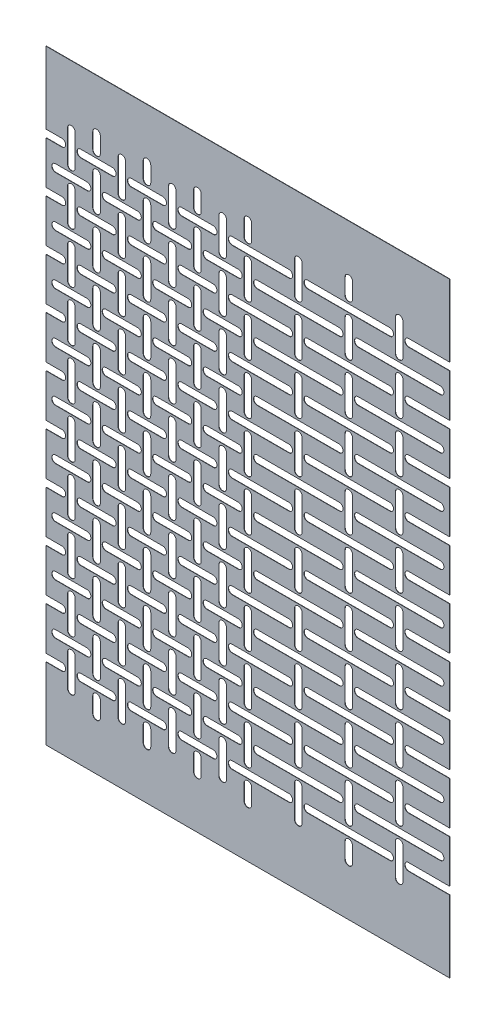
SolidWorks part; units mm, degrees
ref_plane "Front Plane" through (0, 0, 0) normal (0, 0, 1) x (1, 0, 0)
ref_plane "Top Plane" through (0, 0, 0) normal (0, 1, 0) x (1, 0, 0)
ref_plane "Right Plane" through (0, 0, 0) normal (1, 0, 0) x (0, 0, -1)
sketch "Model" plane through (0, 0, 0) normal (0, 0, 1) x (1, 0, 0)
  line L0 (0, 31.5) -> (6.25, 31.5)
  line L1 (0, 28.5) -> (6.25, 28.5)
  line L2 (13.75, 31.5) -> (26.25, 31.5)
  line L3 (13.75, 28.5) -> (26.25, 28.5)
  line L4 (33.75, 31.5) -> (46.25, 31.5)
  line L5 (33.75, 28.5) -> (46.25, 28.5)
  line L6 (53.75, 31.5) -> (66.25, 31.5)
  line L7 (53.75, 28.5) -> (66.25, 28.5)
  line L8 (73.75, 31.5) -> (80, 31.5)
  line L9 (73.75, 28.5) -> (80, 28.5)
  line L10 (3.75, 41.5) -> (16.25, 41.5)
  line L11 (3.75, 38.5) -> (16.25, 38.5)
  line L12 (23.75, 41.5) -> (36.25, 41.5)
  line L13 (23.75, 38.5) -> (36.25, 38.5)
  line L14 (43.75, 41.5) -> (56.25, 41.5)
  line L15 (43.75, 38.5) -> (56.25, 38.5)
  line L16 (63.75, 41.5) -> (76.25, 41.5)
  line L17 (63.75, 38.5) -> (76.25, 38.5)
  line L18 (0, 51.5) -> (6.25, 51.5)
  line L19 (0, 48.5) -> (6.25, 48.5)
  line L20 (13.75, 51.5) -> (26.25, 51.5)
  line L21 (13.75, 48.5) -> (26.25, 48.5)
  line L22 (33.75, 51.5) -> (46.25, 51.5)
  line L23 (33.75, 48.5) -> (46.25, 48.5)
  line L24 (53.75, 51.5) -> (66.25, 51.5)
  line L25 (53.75, 48.5) -> (66.25, 48.5)
  line L26 (73.75, 51.5) -> (80, 51.5)
  line L27 (73.75, 48.5) -> (80, 48.5)
  line L28 (3.75, 61.5) -> (16.25, 61.5)
  line L29 (3.75, 58.5) -> (16.25, 58.5)
  line L30 (23.75, 61.5) -> (36.25, 61.5)
  line L31 (23.75, 58.5) -> (36.25, 58.5)
  line L32 (43.75, 61.5) -> (56.25, 61.5)
  line L33 (43.75, 58.5) -> (56.25, 58.5)
  line L34 (63.75, 61.5) -> (76.25, 61.5)
  line L35 (63.75, 58.5) -> (76.25, 58.5)
  line L36 (0, 71.5) -> (6.25, 71.5)
  line L37 (0, 68.5) -> (6.25, 68.5)
  line L38 (13.75, 71.5) -> (26.25, 71.5)
  line L39 (13.75, 68.5) -> (26.25, 68.5)
  line L40 (33.75, 71.5) -> (46.25, 71.5)
  line L41 (33.75, 68.5) -> (46.25, 68.5)
  line L42 (53.75, 71.5) -> (66.25, 71.5)
  line L43 (53.75, 68.5) -> (66.25, 68.5)
  line L44 (73.75, 71.5) -> (80, 71.5)
  line L45 (73.75, 68.5) -> (80, 68.5)
  line L46 (3.75, 81.5) -> (16.25, 81.5)
  line L47 (3.75, 78.5) -> (16.25, 78.5)
  line L48 (23.75, 81.5) -> (36.25, 81.5)
  line L49 (23.75, 78.5) -> (36.25, 78.5)
  line L50 (43.75, 81.5) -> (56.25, 81.5)
  line L51 (43.75, 78.5) -> (56.25, 78.5)
  line L52 (63.75, 81.5) -> (76.25, 81.5)
  line L53 (63.75, 78.5) -> (76.25, 78.5)
  line L54 (0, 91.5) -> (6.25, 91.5)
  line L55 (0, 88.5) -> (6.25, 88.5)
  line L56 (13.75, 91.5) -> (26.25, 91.5)
  line L57 (13.75, 88.5) -> (26.25, 88.5)
  line L58 (33.75, 91.5) -> (46.25, 91.5)
  line L59 (33.75, 88.5) -> (46.25, 88.5)
  line L60 (53.75, 91.5) -> (66.25, 91.5)
  line L61 (53.75, 88.5) -> (66.25, 88.5)
  line L62 (73.75, 91.5) -> (80, 91.5)
  line L63 (73.75, 88.5) -> (80, 88.5)
  line L64 (3.75, 101.5) -> (16.25, 101.5)
  line L65 (3.75, 98.5) -> (16.25, 98.5)
  line L66 (23.75, 101.5) -> (36.25, 101.5)
  line L67 (23.75, 98.5) -> (36.25, 98.5)
  line L68 (43.75, 101.5) -> (56.25, 101.5)
  line L69 (43.75, 98.5) -> (56.25, 98.5)
  line L70 (63.75, 101.5) -> (76.25, 101.5)
  line L71 (63.75, 98.5) -> (76.25, 98.5)
  line L72 (0, 111.5) -> (6.25, 111.5)
  line L73 (0, 108.5) -> (6.25, 108.5)
  line L74 (13.75, 111.5) -> (26.25, 111.5)
  line L75 (13.75, 108.5) -> (26.25, 108.5)
  line L76 (33.75, 111.5) -> (46.25, 111.5)
  line L77 (33.75, 108.5) -> (46.25, 108.5)
  line L78 (53.75, 111.5) -> (66.25, 111.5)
  line L79 (53.75, 108.5) -> (66.25, 108.5)
  line L80 (73.75, 111.5) -> (80, 111.5)
  line L81 (73.75, 108.5) -> (80, 108.5)
  line L82 (3.75, 121.5) -> (16.25, 121.5)
  line L83 (3.75, 118.5) -> (16.25, 118.5)
  line L84 (23.75, 121.5) -> (36.25, 121.5)
  line L85 (23.75, 118.5) -> (36.25, 118.5)
  line L86 (43.75, 121.5) -> (56.25, 121.5)
  line L87 (43.75, 118.5) -> (56.25, 118.5)
  line L88 (63.75, 121.5) -> (76.25, 121.5)
  line L89 (63.75, 118.5) -> (76.25, 118.5)
  line L90 (0, 131.5) -> (6.25, 131.5)
  line L91 (0, 128.5) -> (6.25, 128.5)
  line L92 (13.75, 131.5) -> (26.25, 131.5)
  line L93 (13.75, 128.5) -> (26.25, 128.5)
  line L94 (33.75, 131.5) -> (46.25, 131.5)
  line L95 (33.75, 128.5) -> (46.25, 128.5)
  line L96 (53.75, 131.5) -> (66.25, 131.5)
  line L97 (53.75, 128.5) -> (66.25, 128.5)
  line L98 (73.75, 131.5) -> (80, 131.5)
  line L99 (73.75, 128.5) -> (80, 128.5)
  line L100 (3.75, 141.5) -> (16.25, 141.5)
  line L101 (3.75, 138.5) -> (16.25, 138.5)
  line L102 (23.75, 141.5) -> (36.25, 141.5)
  line L103 (23.75, 138.5) -> (36.25, 138.5)
  line L104 (43.75, 141.5) -> (56.25, 141.5)
  line L105 (43.75, 138.5) -> (56.25, 138.5)
  line L106 (63.75, 141.5) -> (76.25, 141.5)
  line L107 (63.75, 138.5) -> (76.25, 138.5)
  line L108 (0, 151.5) -> (6.25, 151.5)
  line L109 (0, 148.5) -> (6.25, 148.5)
  line L110 (13.75, 151.5) -> (26.25, 151.5)
  line L111 (13.75, 148.5) -> (26.25, 148.5)
  line L112 (33.75, 151.5) -> (46.25, 151.5)
  line L113 (33.75, 148.5) -> (46.25, 148.5)
  line L114 (53.75, 151.5) -> (66.25, 151.5)
  line L115 (53.75, 148.5) -> (66.25, 148.5)
  line L116 (73.75, 151.5) -> (80, 151.5)
  line L117 (73.75, 148.5) -> (80, 148.5)
  line L118 (3.75, 161.5) -> (16.25, 161.5)
  line L119 (3.75, 158.5) -> (16.25, 158.5)
  line L120 (23.75, 161.5) -> (36.25, 161.5)
  line L121 (23.75, 158.5) -> (36.25, 158.5)
  line L122 (43.75, 161.5) -> (56.25, 161.5)
  line L123 (43.75, 158.5) -> (56.25, 158.5)
  line L124 (63.75, 161.5) -> (76.25, 161.5)
  line L125 (63.75, 158.5) -> (76.25, 158.5)
  line L126 (0, 171.5) -> (6.25, 171.5)
  line L127 (0, 168.5) -> (6.25, 168.5)
  line L128 (13.75, 171.5) -> (26.25, 171.5)
  line L129 (13.75, 168.5) -> (26.25, 168.5)
  line L130 (33.75, 171.5) -> (46.25, 171.5)
  line L131 (33.75, 168.5) -> (46.25, 168.5)
  line L132 (53.75, 171.5) -> (66.25, 171.5)
  line L133 (53.75, 168.5) -> (66.25, 168.5)
  line L134 (73.75, 171.5) -> (80, 171.5)
  line L135 (73.75, 168.5) -> (80, 168.5)
  line L136 (3.75, 181.5) -> (16.25, 181.5)
  line L137 (3.75, 178.5) -> (16.25, 178.5)
  line L138 (23.75, 181.5) -> (36.25, 181.5)
  line L139 (23.75, 178.5) -> (36.25, 178.5)
  line L140 (43.75, 181.5) -> (56.25, 181.5)
  line L141 (43.75, 178.5) -> (56.25, 178.5)
  line L142 (63.75, 181.5) -> (76.25, 181.5)
  line L143 (63.75, 178.5) -> (76.25, 178.5)
  line L144 (0, 191.5) -> (6.25, 191.5)
  line L145 (0, 188.5) -> (6.25, 188.5)
  line L146 (13.75, 191.5) -> (26.25, 191.5)
  line L147 (13.75, 188.5) -> (26.25, 188.5)
  line L148 (33.75, 191.5) -> (46.25, 191.5)
  line L149 (33.75, 188.5) -> (46.25, 188.5)
  line L150 (53.75, 191.5) -> (66.25, 191.5)
  line L151 (53.75, 188.5) -> (66.25, 188.5)
  line L152 (73.75, 191.5) -> (80, 191.5)
  line L153 (73.75, 188.5) -> (80, 188.5)
  line L154 (3.75, 201.5) -> (16.25, 201.5)
  line L155 (3.75, 198.5) -> (16.25, 198.5)
  line L156 (23.75, 201.5) -> (36.25, 201.5)
  line L157 (23.75, 198.5) -> (36.25, 198.5)
  line L158 (43.75, 201.5) -> (56.25, 201.5)
  line L159 (43.75, 198.5) -> (56.25, 198.5)
  line L160 (63.75, 201.5) -> (76.25, 201.5)
  line L161 (63.75, 198.5) -> (76.25, 198.5)
  line L162 (0, 211.5) -> (6.25, 211.5)
  line L163 (0, 208.5) -> (6.25, 208.5)
  line L164 (13.75, 211.5) -> (26.25, 211.5)
  line L165 (13.75, 208.5) -> (26.25, 208.5)
  line L166 (33.75, 211.5) -> (46.25, 211.5)
  line L167 (33.75, 208.5) -> (46.25, 208.5)
  line L168 (53.75, 211.5) -> (66.25, 211.5)
  line L169 (53.75, 208.5) -> (66.25, 208.5)
  line L170 (73.75, 211.5) -> (80, 211.5)
  line L171 (73.75, 208.5) -> (80, 208.5)
  line L172 (11.5, 23.75) -> (11.5, 36.25)
  line L173 (8.5, 23.75) -> (8.5, 36.25)
  line L174 (11.5, 43.75) -> (11.5, 56.25)
  line L175 (8.5, 43.75) -> (8.5, 56.25)
  line L176 (11.5, 63.75) -> (11.5, 76.25)
  line L177 (8.5, 63.75) -> (8.5, 76.25)
  line L178 (11.5, 83.75) -> (11.5, 96.25)
  line L179 (8.5, 83.75) -> (8.5, 96.25)
  line L180 (11.5, 103.75) -> (11.5, 116.25)
  line L181 (8.5, 103.75) -> (8.5, 116.25)
  line L182 (11.5, 123.75) -> (11.5, 136.25)
  line L183 (8.5, 123.75) -> (8.5, 136.25)
  line L184 (11.5, 143.75) -> (11.5, 156.25)
  line L185 (8.5, 143.75) -> (8.5, 156.25)
  line L186 (11.5, 163.75) -> (11.5, 176.25)
  line L187 (8.5, 163.75) -> (8.5, 176.25)
  line L188 (11.5, 183.75) -> (11.5, 196.25)
  line L189 (8.5, 183.75) -> (8.5, 196.25)
  line L190 (11.5, 203.75) -> (11.5, 216.25)
  line L191 (8.5, 203.75) -> (8.5, 216.25)
  line L192 (21.5, 20) -> (21.5, 26.25)
  line L193 (18.5, 20) -> (18.5, 26.25)
  line L194 (21.5, 33.75) -> (21.5, 46.25)
  line L195 (18.5, 33.75) -> (18.5, 46.25)
  line L196 (21.5, 53.75) -> (21.5, 66.25)
  line L197 (18.5, 53.75) -> (18.5, 66.25)
  line L198 (21.5, 73.75) -> (21.5, 86.25)
  line L199 (18.5, 73.75) -> (18.5, 86.25)
  line L200 (21.5, 93.75) -> (21.5, 106.25)
  line L201 (18.5, 93.75) -> (18.5, 106.25)
  line L202 (21.5, 113.75) -> (21.5, 126.25)
  line L203 (18.5, 113.75) -> (18.5, 126.25)
  line L204 (21.5, 133.75) -> (21.5, 146.25)
  line L205 (18.5, 133.75) -> (18.5, 146.25)
  line L206 (21.5, 153.75) -> (21.5, 166.25)
  line L207 (18.5, 153.75) -> (18.5, 166.25)
  line L208 (21.5, 173.75) -> (21.5, 186.25)
  line L209 (18.5, 173.75) -> (18.5, 186.25)
  line L210 (21.5, 193.75) -> (21.5, 206.25)
  line L211 (18.5, 193.75) -> (18.5, 206.25)
  line L212 (21.5, 213.75) -> (21.5, 220)
  line L213 (18.5, 213.75) -> (18.5, 220)
  line L214 (31.5, 23.75) -> (31.5, 36.25)
  line L215 (28.5, 23.75) -> (28.5, 36.25)
  line L216 (31.5, 43.75) -> (31.5, 56.25)
  line L217 (28.5, 43.75) -> (28.5, 56.25)
  line L218 (31.5, 63.75) -> (31.5, 76.25)
  line L219 (28.5, 63.75) -> (28.5, 76.25)
  line L220 (31.5, 83.75) -> (31.5, 96.25)
  line L221 (28.5, 83.75) -> (28.5, 96.25)
  line L222 (31.5, 103.75) -> (31.5, 116.25)
  line L223 (28.5, 103.75) -> (28.5, 116.25)
  line L224 (31.5, 123.75) -> (31.5, 136.25)
  line L225 (28.5, 123.75) -> (28.5, 136.25)
  line L226 (31.5, 143.75) -> (31.5, 156.25)
  line L227 (28.5, 143.75) -> (28.5, 156.25)
  line L228 (31.5, 163.75) -> (31.5, 176.25)
  line L229 (28.5, 163.75) -> (28.5, 176.25)
  line L230 (31.5, 183.75) -> (31.5, 196.25)
  line L231 (28.5, 183.75) -> (28.5, 196.25)
  line L232 (31.5, 203.75) -> (31.5, 216.25)
  line L233 (28.5, 203.75) -> (28.5, 216.25)
  line L234 (41.5, 20) -> (41.5, 26.25)
  line L235 (38.5, 20) -> (38.5, 26.25)
  line L236 (41.5, 33.75) -> (41.5, 46.25)
  line L237 (38.5, 33.75) -> (38.5, 46.25)
  line L238 (41.5, 53.75) -> (41.5, 66.25)
  line L239 (38.5, 53.75) -> (38.5, 66.25)
  line L240 (41.5, 73.75) -> (41.5, 86.25)
  line L241 (38.5, 73.75) -> (38.5, 86.25)
  line L242 (41.5, 93.75) -> (41.5, 106.25)
  line L243 (38.5, 93.75) -> (38.5, 106.25)
  line L244 (41.5, 113.75) -> (41.5, 126.25)
  line L245 (38.5, 113.75) -> (38.5, 126.25)
  line L246 (41.5, 133.75) -> (41.5, 146.25)
  line L247 (38.5, 133.75) -> (38.5, 146.25)
  line L248 (41.5, 153.75) -> (41.5, 166.25)
  line L249 (38.5, 153.75) -> (38.5, 166.25)
  line L250 (41.5, 173.75) -> (41.5, 186.25)
  line L251 (38.5, 173.75) -> (38.5, 186.25)
  line L252 (41.5, 193.75) -> (41.5, 206.25)
  line L253 (38.5, 193.75) -> (38.5, 206.25)
  line L254 (41.5, 213.75) -> (41.5, 220)
  line L255 (38.5, 213.75) -> (38.5, 220)
  line L256 (51.5, 23.75) -> (51.5, 36.25)
  line L257 (48.5, 23.75) -> (48.5, 36.25)
  line L258 (51.5, 43.75) -> (51.5, 56.25)
  line L259 (48.5, 43.75) -> (48.5, 56.25)
  line L260 (51.5, 63.75) -> (51.5, 76.25)
  line L261 (48.5, 63.75) -> (48.5, 76.25)
  line L262 (51.5, 83.75) -> (51.5, 96.25)
  line L263 (48.5, 83.75) -> (48.5, 96.25)
  line L264 (51.5, 103.75) -> (51.5, 116.25)
  line L265 (48.5, 103.75) -> (48.5, 116.25)
  line L266 (51.5, 123.75) -> (51.5, 136.25)
  line L267 (48.5, 123.75) -> (48.5, 136.25)
  line L268 (51.5, 143.75) -> (51.5, 156.25)
  line L269 (48.5, 143.75) -> (48.5, 156.25)
  line L270 (51.5, 163.75) -> (51.5, 176.25)
  line L271 (48.5, 163.75) -> (48.5, 176.25)
  line L272 (51.5, 183.75) -> (51.5, 196.25)
  line L273 (48.5, 183.75) -> (48.5, 196.25)
  line L274 (51.5, 203.75) -> (51.5, 216.25)
  line L275 (48.5, 203.75) -> (48.5, 216.25)
  line L276 (61.5, 20) -> (61.5, 26.25)
  line L277 (58.5, 20) -> (58.5, 26.25)
  line L278 (61.5, 33.75) -> (61.5, 46.25)
  line L279 (58.5, 33.75) -> (58.5, 46.25)
  line L280 (61.5, 53.75) -> (61.5, 66.25)
  line L281 (58.5, 53.75) -> (58.5, 66.25)
  line L282 (61.5, 73.75) -> (61.5, 86.25)
  line L283 (58.5, 73.75) -> (58.5, 86.25)
  line L284 (61.5, 93.75) -> (61.5, 106.25)
  line L285 (58.5, 93.75) -> (58.5, 106.25)
  line L286 (61.5, 113.75) -> (61.5, 126.25)
  line L287 (58.5, 113.75) -> (58.5, 126.25)
  line L288 (61.5, 133.75) -> (61.5, 146.25)
  line L289 (58.5, 133.75) -> (58.5, 146.25)
  line L290 (61.5, 153.75) -> (61.5, 166.25)
  line L291 (58.5, 153.75) -> (58.5, 166.25)
  line L292 (61.5, 173.75) -> (61.5, 186.25)
  line L293 (58.5, 173.75) -> (58.5, 186.25)
  line L294 (61.5, 193.75) -> (61.5, 206.25)
  line L295 (58.5, 193.75) -> (58.5, 206.25)
  line L296 (61.5, 213.75) -> (61.5, 220)
  line L297 (58.5, 213.75) -> (58.5, 220)
  line L298 (71.5, 23.75) -> (71.5, 36.25)
  line L299 (68.5, 23.75) -> (68.5, 36.25)
  line L300 (71.5, 43.75) -> (71.5, 56.25)
  line L301 (68.5, 43.75) -> (68.5, 56.25)
  line L302 (71.5, 63.75) -> (71.5, 76.25)
  line L303 (68.5, 63.75) -> (68.5, 76.25)
  line L304 (71.5, 83.75) -> (71.5, 96.25)
  line L305 (68.5, 83.75) -> (68.5, 96.25)
  line L306 (71.5, 103.75) -> (71.5, 116.25)
  line L307 (68.5, 103.75) -> (68.5, 116.25)
  line L308 (71.5, 123.75) -> (71.5, 136.25)
  line L309 (68.5, 123.75) -> (68.5, 136.25)
  line L310 (71.5, 143.75) -> (71.5, 156.25)
  line L311 (68.5, 143.75) -> (68.5, 156.25)
  line L312 (71.5, 163.75) -> (71.5, 176.25)
  line L313 (68.5, 163.75) -> (68.5, 176.25)
  line L314 (71.5, 183.75) -> (71.5, 196.25)
  line L315 (68.5, 183.75) -> (68.5, 196.25)
  line L316 (71.5, 203.75) -> (71.5, 216.25)
  line L317 (68.5, 203.75) -> (68.5, 216.25)
  line L318 (81.5, 20) -> (81.5, 26.25)
  line L319 (78.5, 20) -> (78.5, 26.25)
  line L320 (81.5, 33.75) -> (81.5, 46.25)
  line L321 (78.5, 33.75) -> (78.5, 46.25)
  line L322 (81.5, 53.75) -> (81.5, 66.25)
  line L323 (78.5, 53.75) -> (78.5, 66.25)
  line L324 (81.5, 73.75) -> (81.5, 86.25)
  line L325 (78.5, 73.75) -> (78.5, 86.25)
  line L326 (81.5, 93.75) -> (81.5, 106.25)
  line L327 (78.5, 93.75) -> (78.5, 106.25)
  line L328 (81.5, 113.75) -> (81.5, 126.25)
  line L329 (78.5, 113.75) -> (78.5, 126.25)
  line L330 (81.5, 133.75) -> (81.5, 146.25)
  line L331 (78.5, 133.75) -> (78.5, 146.25)
  line L332 (81.5, 153.75) -> (81.5, 166.25)
  line L333 (78.5, 153.75) -> (78.5, 166.25)
  line L334 (81.5, 173.75) -> (81.5, 186.25)
  line L335 (78.5, 173.75) -> (78.5, 186.25)
  line L336 (81.5, 193.75) -> (81.5, 206.25)
  line L337 (78.5, 193.75) -> (78.5, 206.25)
  line L338 (81.5, 213.75) -> (81.5, 220)
  line L339 (78.5, 213.75) -> (78.5, 220)
  line L340 (0, 0) -> (80, 0)
  line L341 (80, 240) -> (0, 240)
  line L342 (0, 0) -> (0, 28.5)
  line L343 (0, 31.5) -> (0, 48.5)
  line L344 (0, 51.5) -> (0, 68.5)
  line L345 (0, 71.5) -> (0, 88.5)
  line L346 (0, 91.5) -> (0, 108.5)
  line L347 (0, 111.5) -> (0, 128.5)
  line L348 (0, 131.5) -> (0, 148.5)
  line L349 (0, 151.5) -> (0, 168.5)
  line L350 (0, 171.5) -> (0, 188.5)
  line L351 (0, 191.5) -> (0, 208.5)
  line L352 (0, 211.5) -> (0, 240)
  line L353 (80, 31.5) -> (96.25, 31.5)
  line L354 (80, 28.5) -> (96.25, 28.5)
  line L355 (103.75, 31.5) -> (136.25, 31.5)
  line L356 (103.75, 28.5) -> (136.25, 28.5)
  line L357 (143.75, 31.5) -> (160, 31.5)
  line L358 (143.75, 28.5) -> (160, 28.5)
  line L359 (83.75, 41.5) -> (116.25, 41.5)
  line L360 (83.75, 38.5) -> (116.25, 38.5)
  line L361 (123.75, 41.5) -> (156.25, 41.5)
  line L362 (123.75, 38.5) -> (156.25, 38.5)
  line L363 (80, 51.5) -> (96.25, 51.5)
  line L364 (80, 48.5) -> (96.25, 48.5)
  line L365 (103.75, 51.5) -> (136.25, 51.5)
  line L366 (103.75, 48.5) -> (136.25, 48.5)
  line L367 (143.75, 51.5) -> (160, 51.5)
  line L368 (143.75, 48.5) -> (160, 48.5)
  line L369 (83.75, 61.5) -> (116.25, 61.5)
  line L370 (83.75, 58.5) -> (116.25, 58.5)
  line L371 (123.75, 61.5) -> (156.25, 61.5)
  line L372 (123.75, 58.5) -> (156.25, 58.5)
  line L373 (80, 71.5) -> (96.25, 71.5)
  line L374 (80, 68.5) -> (96.25, 68.5)
  line L375 (103.75, 71.5) -> (136.25, 71.5)
  line L376 (103.75, 68.5) -> (136.25, 68.5)
  line L377 (143.75, 71.5) -> (160, 71.5)
  line L378 (143.75, 68.5) -> (160, 68.5)
  line L379 (83.75, 81.5) -> (116.25, 81.5)
  line L380 (83.75, 78.5) -> (116.25, 78.5)
  line L381 (123.75, 81.5) -> (156.25, 81.5)
  line L382 (123.75, 78.5) -> (156.25, 78.5)
  line L383 (80, 91.5) -> (96.25, 91.5)
  line L384 (80, 88.5) -> (96.25, 88.5)
  line L385 (103.75, 91.5) -> (136.25, 91.5)
  line L386 (103.75, 88.5) -> (136.25, 88.5)
  line L387 (143.75, 91.5) -> (160, 91.5)
  line L388 (143.75, 88.5) -> (160, 88.5)
  line L389 (83.75, 101.5) -> (116.25, 101.5)
  line L390 (83.75, 98.5) -> (116.25, 98.5)
  line L391 (123.75, 101.5) -> (156.25, 101.5)
  line L392 (123.75, 98.5) -> (156.25, 98.5)
  line L393 (80, 111.5) -> (96.25, 111.5)
  line L394 (80, 108.5) -> (96.25, 108.5)
  line L395 (103.75, 111.5) -> (136.25, 111.5)
  line L396 (103.75, 108.5) -> (136.25, 108.5)
  line L397 (143.75, 111.5) -> (160, 111.5)
  line L398 (143.75, 108.5) -> (160, 108.5)
  line L399 (83.75, 121.5) -> (116.25, 121.5)
  line L400 (83.75, 118.5) -> (116.25, 118.5)
  line L401 (123.75, 121.5) -> (156.25, 121.5)
  line L402 (123.75, 118.5) -> (156.25, 118.5)
  line L403 (80, 131.5) -> (96.25, 131.5)
  line L404 (80, 128.5) -> (96.25, 128.5)
  line L405 (103.75, 131.5) -> (136.25, 131.5)
  line L406 (103.75, 128.5) -> (136.25, 128.5)
  line L407 (143.75, 131.5) -> (160, 131.5)
  line L408 (143.75, 128.5) -> (160, 128.5)
  line L409 (83.75, 141.5) -> (116.25, 141.5)
  line L410 (83.75, 138.5) -> (116.25, 138.5)
  line L411 (123.75, 141.5) -> (156.25, 141.5)
  line L412 (123.75, 138.5) -> (156.25, 138.5)
  line L413 (80, 151.5) -> (96.25, 151.5)
  line L414 (80, 148.5) -> (96.25, 148.5)
  line L415 (103.75, 151.5) -> (136.25, 151.5)
  line L416 (103.75, 148.5) -> (136.25, 148.5)
  line L417 (143.75, 151.5) -> (160, 151.5)
  line L418 (143.75, 148.5) -> (160, 148.5)
  line L419 (83.75, 161.5) -> (116.25, 161.5)
  line L420 (83.75, 158.5) -> (116.25, 158.5)
  line L421 (123.75, 161.5) -> (156.25, 161.5)
  line L422 (123.75, 158.5) -> (156.25, 158.5)
  line L423 (80, 171.5) -> (96.25, 171.5)
  line L424 (80, 168.5) -> (96.25, 168.5)
  line L425 (103.75, 171.5) -> (136.25, 171.5)
  line L426 (103.75, 168.5) -> (136.25, 168.5)
  line L427 (143.75, 171.5) -> (160, 171.5)
  line L428 (143.75, 168.5) -> (160, 168.5)
  line L429 (83.75, 181.5) -> (116.25, 181.5)
  line L430 (83.75, 178.5) -> (116.25, 178.5)
  line L431 (123.75, 181.5) -> (156.25, 181.5)
  line L432 (123.75, 178.5) -> (156.25, 178.5)
  line L433 (80, 191.5) -> (96.25, 191.5)
  line L434 (80, 188.5) -> (96.25, 188.5)
  line L435 (103.75, 191.5) -> (136.25, 191.5)
  line L436 (103.75, 188.5) -> (136.25, 188.5)
  line L437 (143.75, 191.5) -> (160, 191.5)
  line L438 (143.75, 188.5) -> (160, 188.5)
  line L439 (83.75, 201.5) -> (116.25, 201.5)
  line L440 (83.75, 198.5) -> (116.25, 198.5)
  line L441 (123.75, 201.5) -> (156.25, 201.5)
  line L442 (123.75, 198.5) -> (156.25, 198.5)
  line L443 (80, 211.5) -> (96.25, 211.5)
  line L444 (80, 208.5) -> (96.25, 208.5)
  line L445 (103.75, 211.5) -> (136.25, 211.5)
  line L446 (103.75, 208.5) -> (136.25, 208.5)
  line L447 (143.75, 211.5) -> (160, 211.5)
  line L448 (143.75, 208.5) -> (160, 208.5)
  line L449 (101.5, 23.75) -> (101.5, 36.25)
  line L450 (98.5, 23.75) -> (98.5, 36.25)
  line L451 (101.5, 43.75) -> (101.5, 56.25)
  line L452 (98.5, 43.75) -> (98.5, 56.25)
  line L453 (101.5, 63.75) -> (101.5, 76.25)
  line L454 (98.5, 63.75) -> (98.5, 76.25)
  line L455 (101.5, 83.75) -> (101.5, 96.25)
  line L456 (98.5, 83.75) -> (98.5, 96.25)
  line L457 (101.5, 103.75) -> (101.5, 116.25)
  line L458 (98.5, 103.75) -> (98.5, 116.25)
  line L459 (101.5, 123.75) -> (101.5, 136.25)
  line L460 (98.5, 123.75) -> (98.5, 136.25)
  line L461 (101.5, 143.75) -> (101.5, 156.25)
  line L462 (98.5, 143.75) -> (98.5, 156.25)
  line L463 (101.5, 163.75) -> (101.5, 176.25)
  line L464 (98.5, 163.75) -> (98.5, 176.25)
  line L465 (101.5, 183.75) -> (101.5, 196.25)
  line L466 (98.5, 183.75) -> (98.5, 196.25)
  line L467 (101.5, 203.75) -> (101.5, 216.25)
  line L468 (98.5, 203.75) -> (98.5, 216.25)
  line L469 (121.5, 20) -> (121.5, 26.25)
  line L470 (118.5, 20) -> (118.5, 26.25)
  line L471 (121.5, 33.75) -> (121.5, 46.25)
  line L472 (118.5, 33.75) -> (118.5, 46.25)
  line L473 (121.5, 53.75) -> (121.5, 66.25)
  line L474 (118.5, 53.75) -> (118.5, 66.25)
  line L475 (121.5, 73.75) -> (121.5, 86.25)
  line L476 (118.5, 73.75) -> (118.5, 86.25)
  line L477 (121.5, 93.75) -> (121.5, 106.25)
  line L478 (118.5, 93.75) -> (118.5, 106.25)
  line L479 (121.5, 113.75) -> (121.5, 126.25)
  line L480 (118.5, 113.75) -> (118.5, 126.25)
  line L481 (121.5, 133.75) -> (121.5, 146.25)
  line L482 (118.5, 133.75) -> (118.5, 146.25)
  line L483 (121.5, 153.75) -> (121.5, 166.25)
  line L484 (118.5, 153.75) -> (118.5, 166.25)
  line L485 (121.5, 173.75) -> (121.5, 186.25)
  line L486 (118.5, 173.75) -> (118.5, 186.25)
  line L487 (121.5, 193.75) -> (121.5, 206.25)
  line L488 (118.5, 193.75) -> (118.5, 206.25)
  line L489 (121.5, 213.75) -> (121.5, 220)
  line L490 (118.5, 213.75) -> (118.5, 220)
  line L491 (141.5, 23.75) -> (141.5, 36.25)
  line L492 (138.5, 23.75) -> (138.5, 36.25)
  line L493 (141.5, 43.75) -> (141.5, 56.25)
  line L494 (138.5, 43.75) -> (138.5, 56.25)
  line L495 (141.5, 63.75) -> (141.5, 76.25)
  line L496 (138.5, 63.75) -> (138.5, 76.25)
  line L497 (141.5, 83.75) -> (141.5, 96.25)
  line L498 (138.5, 83.75) -> (138.5, 96.25)
  line L499 (141.5, 103.75) -> (141.5, 116.25)
  line L500 (138.5, 103.75) -> (138.5, 116.25)
  line L501 (141.5, 123.75) -> (141.5, 136.25)
  line L502 (138.5, 123.75) -> (138.5, 136.25)
  line L503 (141.5, 143.75) -> (141.5, 156.25)
  line L504 (138.5, 143.75) -> (138.5, 156.25)
  line L505 (141.5, 163.75) -> (141.5, 176.25)
  line L506 (138.5, 163.75) -> (138.5, 176.25)
  line L507 (141.5, 183.75) -> (141.5, 196.25)
  line L508 (138.5, 183.75) -> (138.5, 196.25)
  line L509 (141.5, 203.75) -> (141.5, 216.25)
  line L510 (138.5, 203.75) -> (138.5, 216.25)
  line L511 (80, 0) -> (160, 0)
  line L512 (160, 0) -> (160, 28.5)
  line L513 (160, 31.5) -> (160, 48.5)
  line L514 (160, 51.5) -> (160, 68.5)
  line L515 (160, 71.5) -> (160, 88.5)
  line L516 (160, 91.5) -> (160, 108.5)
  line L517 (160, 111.5) -> (160, 128.5)
  line L518 (160, 131.5) -> (160, 148.5)
  line L519 (160, 151.5) -> (160, 168.5)
  line L520 (160, 171.5) -> (160, 188.5)
  line L521 (160, 191.5) -> (160, 208.5)
  line L522 (160, 211.5) -> (160, 240)
  line L523 (160, 240) -> (80, 240)
  arc A0 (6.25, 28.5) -> (6.25, 31.5) centre (6.25, 30) ccw
  arc A1 (13.75, 31.5) -> (13.75, 28.5) centre (13.75, 30) ccw
  arc A2 (26.25, 28.5) -> (26.25, 31.5) centre (26.25, 30) ccw
  arc A3 (33.75, 31.5) -> (33.75, 28.5) centre (33.75, 30) ccw
  arc A4 (46.25, 28.5) -> (46.25, 31.5) centre (46.25, 30) ccw
  arc A5 (53.75, 31.5) -> (53.75, 28.5) centre (53.75, 30) ccw
  arc A6 (66.25, 28.5) -> (66.25, 31.5) centre (66.25, 30) ccw
  arc A7 (73.75, 31.5) -> (73.75, 28.5) centre (73.75, 30) ccw
  arc A8 (3.75, 41.5) -> (3.75, 38.5) centre (3.75, 40) ccw
  arc A9 (16.25, 38.5) -> (16.25, 41.5) centre (16.25, 40) ccw
  arc A10 (23.75, 41.5) -> (23.75, 38.5) centre (23.75, 40) ccw
  arc A11 (36.25, 38.5) -> (36.25, 41.5) centre (36.25, 40) ccw
  arc A12 (43.75, 41.5) -> (43.75, 38.5) centre (43.75, 40) ccw
  arc A13 (56.25, 38.5) -> (56.25, 41.5) centre (56.25, 40) ccw
  arc A14 (63.75, 41.5) -> (63.75, 38.5) centre (63.75, 40) ccw
  arc A15 (76.25, 38.5) -> (76.25, 41.5) centre (76.25, 40) ccw
  arc A16 (6.25, 48.5) -> (6.25, 51.5) centre (6.25, 50) ccw
  arc A17 (13.75, 51.5) -> (13.75, 48.5) centre (13.75, 50) ccw
  arc A18 (26.25, 48.5) -> (26.25, 51.5) centre (26.25, 50) ccw
  arc A19 (33.75, 51.5) -> (33.75, 48.5) centre (33.75, 50) ccw
  arc A20 (46.25, 48.5) -> (46.25, 51.5) centre (46.25, 50) ccw
  arc A21 (53.75, 51.5) -> (53.75, 48.5) centre (53.75, 50) ccw
  arc A22 (66.25, 48.5) -> (66.25, 51.5) centre (66.25, 50) ccw
  arc A23 (73.75, 51.5) -> (73.75, 48.5) centre (73.75, 50) ccw
  arc A24 (3.75, 61.5) -> (3.75, 58.5) centre (3.75, 60) ccw
  arc A25 (16.25, 58.5) -> (16.25, 61.5) centre (16.25, 60) ccw
  arc A26 (23.75, 61.5) -> (23.75, 58.5) centre (23.75, 60) ccw
  arc A27 (36.25, 58.5) -> (36.25, 61.5) centre (36.25, 60) ccw
  arc A28 (43.75, 61.5) -> (43.75, 58.5) centre (43.75, 60) ccw
  arc A29 (56.25, 58.5) -> (56.25, 61.5) centre (56.25, 60) ccw
  arc A30 (63.75, 61.5) -> (63.75, 58.5) centre (63.75, 60) ccw
  arc A31 (76.25, 58.5) -> (76.25, 61.5) centre (76.25, 60) ccw
  arc A32 (6.25, 68.5) -> (6.25, 71.5) centre (6.25, 70) ccw
  arc A33 (13.75, 71.5) -> (13.75, 68.5) centre (13.75, 70) ccw
  arc A34 (26.25, 68.5) -> (26.25, 71.5) centre (26.25, 70) ccw
  arc A35 (33.75, 71.5) -> (33.75, 68.5) centre (33.75, 70) ccw
  arc A36 (46.25, 68.5) -> (46.25, 71.5) centre (46.25, 70) ccw
  arc A37 (53.75, 71.5) -> (53.75, 68.5) centre (53.75, 70) ccw
  arc A38 (66.25, 68.5) -> (66.25, 71.5) centre (66.25, 70) ccw
  arc A39 (73.75, 71.5) -> (73.75, 68.5) centre (73.75, 70) ccw
  arc A40 (3.75, 81.5) -> (3.75, 78.5) centre (3.75, 80) ccw
  arc A41 (16.25, 78.5) -> (16.25, 81.5) centre (16.25, 80) ccw
  arc A42 (23.75, 81.5) -> (23.75, 78.5) centre (23.75, 80) ccw
  arc A43 (36.25, 78.5) -> (36.25, 81.5) centre (36.25, 80) ccw
  arc A44 (43.75, 81.5) -> (43.75, 78.5) centre (43.75, 80) ccw
  arc A45 (56.25, 78.5) -> (56.25, 81.5) centre (56.25, 80) ccw
  arc A46 (63.75, 81.5) -> (63.75, 78.5) centre (63.75, 80) ccw
  arc A47 (76.25, 78.5) -> (76.25, 81.5) centre (76.25, 80) ccw
  arc A48 (6.25, 88.5) -> (6.25, 91.5) centre (6.25, 90) ccw
  arc A49 (13.75, 91.5) -> (13.75, 88.5) centre (13.75, 90) ccw
  arc A50 (26.25, 88.5) -> (26.25, 91.5) centre (26.25, 90) ccw
  arc A51 (33.75, 91.5) -> (33.75, 88.5) centre (33.75, 90) ccw
  arc A52 (46.25, 88.5) -> (46.25, 91.5) centre (46.25, 90) ccw
  arc A53 (53.75, 91.5) -> (53.75, 88.5) centre (53.75, 90) ccw
  arc A54 (66.25, 88.5) -> (66.25, 91.5) centre (66.25, 90) ccw
  arc A55 (73.75, 91.5) -> (73.75, 88.5) centre (73.75, 90) ccw
  arc A56 (3.75, 101.5) -> (3.75, 98.5) centre (3.75, 100) ccw
  arc A57 (16.25, 98.5) -> (16.25, 101.5) centre (16.25, 100) ccw
  arc A58 (23.75, 101.5) -> (23.75, 98.5) centre (23.75, 100) ccw
  arc A59 (36.25, 98.5) -> (36.25, 101.5) centre (36.25, 100) ccw
  arc A60 (43.75, 101.5) -> (43.75, 98.5) centre (43.75, 100) ccw
  arc A61 (56.25, 98.5) -> (56.25, 101.5) centre (56.25, 100) ccw
  arc A62 (63.75, 101.5) -> (63.75, 98.5) centre (63.75, 100) ccw
  arc A63 (76.25, 98.5) -> (76.25, 101.5) centre (76.25, 100) ccw
  arc A64 (6.25, 108.5) -> (6.25, 111.5) centre (6.25, 110) ccw
  arc A65 (13.75, 111.5) -> (13.75, 108.5) centre (13.75, 110) ccw
  arc A66 (26.25, 108.5) -> (26.25, 111.5) centre (26.25, 110) ccw
  arc A67 (33.75, 111.5) -> (33.75, 108.5) centre (33.75, 110) ccw
  arc A68 (46.25, 108.5) -> (46.25, 111.5) centre (46.25, 110) ccw
  arc A69 (53.75, 111.5) -> (53.75, 108.5) centre (53.75, 110) ccw
  arc A70 (66.25, 108.5) -> (66.25, 111.5) centre (66.25, 110) ccw
  arc A71 (73.75, 111.5) -> (73.75, 108.5) centre (73.75, 110) ccw
  arc A72 (3.75, 121.5) -> (3.75, 118.5) centre (3.75, 120) ccw
  arc A73 (16.25, 118.5) -> (16.25, 121.5) centre (16.25, 120) ccw
  arc A74 (23.75, 121.5) -> (23.75, 118.5) centre (23.75, 120) ccw
  arc A75 (36.25, 118.5) -> (36.25, 121.5) centre (36.25, 120) ccw
  arc A76 (43.75, 121.5) -> (43.75, 118.5) centre (43.75, 120) ccw
  arc A77 (56.25, 118.5) -> (56.25, 121.5) centre (56.25, 120) ccw
  arc A78 (63.75, 121.5) -> (63.75, 118.5) centre (63.75, 120) ccw
  arc A79 (76.25, 118.5) -> (76.25, 121.5) centre (76.25, 120) ccw
  arc A80 (6.25, 128.5) -> (6.25, 131.5) centre (6.25, 130) ccw
  arc A81 (13.75, 131.5) -> (13.75, 128.5) centre (13.75, 130) ccw
  arc A82 (26.25, 128.5) -> (26.25, 131.5) centre (26.25, 130) ccw
  arc A83 (33.75, 131.5) -> (33.75, 128.5) centre (33.75, 130) ccw
  arc A84 (46.25, 128.5) -> (46.25, 131.5) centre (46.25, 130) ccw
  arc A85 (53.75, 131.5) -> (53.75, 128.5) centre (53.75, 130) ccw
  arc A86 (66.25, 128.5) -> (66.25, 131.5) centre (66.25, 130) ccw
  arc A87 (73.75, 131.5) -> (73.75, 128.5) centre (73.75, 130) ccw
  arc A88 (3.75, 141.5) -> (3.75, 138.5) centre (3.75, 140) ccw
  arc A89 (16.25, 138.5) -> (16.25, 141.5) centre (16.25, 140) ccw
  arc A90 (23.75, 141.5) -> (23.75, 138.5) centre (23.75, 140) ccw
  arc A91 (36.25, 138.5) -> (36.25, 141.5) centre (36.25, 140) ccw
  arc A92 (43.75, 141.5) -> (43.75, 138.5) centre (43.75, 140) ccw
  arc A93 (56.25, 138.5) -> (56.25, 141.5) centre (56.25, 140) ccw
  arc A94 (63.75, 141.5) -> (63.75, 138.5) centre (63.75, 140) ccw
  arc A95 (76.25, 138.5) -> (76.25, 141.5) centre (76.25, 140) ccw
  arc A96 (6.25, 148.5) -> (6.25, 151.5) centre (6.25, 150) ccw
  arc A97 (13.75, 151.5) -> (13.75, 148.5) centre (13.75, 150) ccw
  arc A98 (26.25, 148.5) -> (26.25, 151.5) centre (26.25, 150) ccw
  arc A99 (33.75, 151.5) -> (33.75, 148.5) centre (33.75, 150) ccw
  arc A100 (46.25, 148.5) -> (46.25, 151.5) centre (46.25, 150) ccw
  arc A101 (53.75, 151.5) -> (53.75, 148.5) centre (53.75, 150) ccw
  arc A102 (66.25, 148.5) -> (66.25, 151.5) centre (66.25, 150) ccw
  arc A103 (73.75, 151.5) -> (73.75, 148.5) centre (73.75, 150) ccw
  arc A104 (3.75, 161.5) -> (3.75, 158.5) centre (3.75, 160) ccw
  arc A105 (16.25, 158.5) -> (16.25, 161.5) centre (16.25, 160) ccw
  arc A106 (23.75, 161.5) -> (23.75, 158.5) centre (23.75, 160) ccw
  arc A107 (36.25, 158.5) -> (36.25, 161.5) centre (36.25, 160) ccw
  arc A108 (43.75, 161.5) -> (43.75, 158.5) centre (43.75, 160) ccw
  arc A109 (56.25, 158.5) -> (56.25, 161.5) centre (56.25, 160) ccw
  arc A110 (63.75, 161.5) -> (63.75, 158.5) centre (63.75, 160) ccw
  arc A111 (76.25, 158.5) -> (76.25, 161.5) centre (76.25, 160) ccw
  arc A112 (6.25, 168.5) -> (6.25, 171.5) centre (6.25, 170) ccw
  arc A113 (13.75, 171.5) -> (13.75, 168.5) centre (13.75, 170) ccw
  arc A114 (26.25, 168.5) -> (26.25, 171.5) centre (26.25, 170) ccw
  arc A115 (33.75, 171.5) -> (33.75, 168.5) centre (33.75, 170) ccw
  arc A116 (46.25, 168.5) -> (46.25, 171.5) centre (46.25, 170) ccw
  arc A117 (53.75, 171.5) -> (53.75, 168.5) centre (53.75, 170) ccw
  arc A118 (66.25, 168.5) -> (66.25, 171.5) centre (66.25, 170) ccw
  arc A119 (73.75, 171.5) -> (73.75, 168.5) centre (73.75, 170) ccw
  arc A120 (3.75, 181.5) -> (3.75, 178.5) centre (3.75, 180) ccw
  arc A121 (16.25, 178.5) -> (16.25, 181.5) centre (16.25, 180) ccw
  arc A122 (23.75, 181.5) -> (23.75, 178.5) centre (23.75, 180) ccw
  arc A123 (36.25, 178.5) -> (36.25, 181.5) centre (36.25, 180) ccw
  arc A124 (43.75, 181.5) -> (43.75, 178.5) centre (43.75, 180) ccw
  arc A125 (56.25, 178.5) -> (56.25, 181.5) centre (56.25, 180) ccw
  arc A126 (63.75, 181.5) -> (63.75, 178.5) centre (63.75, 180) ccw
  arc A127 (76.25, 178.5) -> (76.25, 181.5) centre (76.25, 180) ccw
  arc A128 (6.25, 188.5) -> (6.25, 191.5) centre (6.25, 190) ccw
  arc A129 (13.75, 191.5) -> (13.75, 188.5) centre (13.75, 190) ccw
  arc A130 (26.25, 188.5) -> (26.25, 191.5) centre (26.25, 190) ccw
  arc A131 (33.75, 191.5) -> (33.75, 188.5) centre (33.75, 190) ccw
  arc A132 (46.25, 188.5) -> (46.25, 191.5) centre (46.25, 190) ccw
  arc A133 (53.75, 191.5) -> (53.75, 188.5) centre (53.75, 190) ccw
  arc A134 (66.25, 188.5) -> (66.25, 191.5) centre (66.25, 190) ccw
  arc A135 (73.75, 191.5) -> (73.75, 188.5) centre (73.75, 190) ccw
  arc A136 (3.75, 201.5) -> (3.75, 198.5) centre (3.75, 200) ccw
  arc A137 (16.25, 198.5) -> (16.25, 201.5) centre (16.25, 200) ccw
  arc A138 (23.75, 201.5) -> (23.75, 198.5) centre (23.75, 200) ccw
  arc A139 (36.25, 198.5) -> (36.25, 201.5) centre (36.25, 200) ccw
  arc A140 (43.75, 201.5) -> (43.75, 198.5) centre (43.75, 200) ccw
  arc A141 (56.25, 198.5) -> (56.25, 201.5) centre (56.25, 200) ccw
  arc A142 (63.75, 201.5) -> (63.75, 198.5) centre (63.75, 200) ccw
  arc A143 (76.25, 198.5) -> (76.25, 201.5) centre (76.25, 200) ccw
  arc A144 (6.25, 208.5) -> (6.25, 211.5) centre (6.25, 210) ccw
  arc A145 (13.75, 211.5) -> (13.75, 208.5) centre (13.75, 210) ccw
  arc A146 (26.25, 208.5) -> (26.25, 211.5) centre (26.25, 210) ccw
  arc A147 (33.75, 211.5) -> (33.75, 208.5) centre (33.75, 210) ccw
  arc A148 (46.25, 208.5) -> (46.25, 211.5) centre (46.25, 210) ccw
  arc A149 (53.75, 211.5) -> (53.75, 208.5) centre (53.75, 210) ccw
  arc A150 (66.25, 208.5) -> (66.25, 211.5) centre (66.25, 210) ccw
  arc A151 (73.75, 211.5) -> (73.75, 208.5) centre (73.75, 210) ccw
  arc A152 (8.5, 23.75) -> (11.5, 23.75) centre (10, 23.75) ccw
  arc A153 (11.5, 36.25) -> (8.5, 36.25) centre (10, 36.25) ccw
  arc A154 (8.5, 43.75) -> (11.5, 43.75) centre (10, 43.75) ccw
  arc A155 (11.5, 56.25) -> (8.5, 56.25) centre (10, 56.25) ccw
  arc A156 (8.5, 63.75) -> (11.5, 63.75) centre (10, 63.75) ccw
  arc A157 (11.5, 76.25) -> (8.5, 76.25) centre (10, 76.25) ccw
  arc A158 (8.5, 83.75) -> (11.5, 83.75) centre (10, 83.75) ccw
  arc A159 (11.5, 96.25) -> (8.5, 96.25) centre (10, 96.25) ccw
  arc A160 (8.5, 103.75) -> (11.5, 103.75) centre (10, 103.75) ccw
  arc A161 (11.5, 116.25) -> (8.5, 116.25) centre (10, 116.25) ccw
  arc A162 (8.5, 123.75) -> (11.5, 123.75) centre (10, 123.75) ccw
  arc A163 (11.5, 136.25) -> (8.5, 136.25) centre (10, 136.25) ccw
  arc A164 (8.5, 143.75) -> (11.5, 143.75) centre (10, 143.75) ccw
  arc A165 (11.5, 156.25) -> (8.5, 156.25) centre (10, 156.25) ccw
  arc A166 (8.5, 163.75) -> (11.5, 163.75) centre (10, 163.75) ccw
  arc A167 (11.5, 176.25) -> (8.5, 176.25) centre (10, 176.25) ccw
  arc A168 (8.5, 183.75) -> (11.5, 183.75) centre (10, 183.75) ccw
  arc A169 (11.5, 196.25) -> (8.5, 196.25) centre (10, 196.25) ccw
  arc A170 (8.5, 203.75) -> (11.5, 203.75) centre (10, 203.75) ccw
  arc A171 (11.5, 216.25) -> (8.5, 216.25) centre (10, 216.25) ccw
  arc A172 (18.5, 20) -> (21.5, 20) centre (20, 20) ccw
  arc A173 (21.5, 26.25) -> (18.5, 26.25) centre (20, 26.25) ccw
  arc A174 (18.5, 33.75) -> (21.5, 33.75) centre (20, 33.75) ccw
  arc A175 (21.5, 46.25) -> (18.5, 46.25) centre (20, 46.25) ccw
  arc A176 (18.5, 53.75) -> (21.5, 53.75) centre (20, 53.75) ccw
  arc A177 (21.5, 66.25) -> (18.5, 66.25) centre (20, 66.25) ccw
  arc A178 (18.5, 73.75) -> (21.5, 73.75) centre (20, 73.75) ccw
  arc A179 (21.5, 86.25) -> (18.5, 86.25) centre (20, 86.25) ccw
  arc A180 (18.5, 93.75) -> (21.5, 93.75) centre (20, 93.75) ccw
  arc A181 (21.5, 106.25) -> (18.5, 106.25) centre (20, 106.25) ccw
  arc A182 (18.5, 113.75) -> (21.5, 113.75) centre (20, 113.75) ccw
  arc A183 (21.5, 126.25) -> (18.5, 126.25) centre (20, 126.25) ccw
  arc A184 (18.5, 133.75) -> (21.5, 133.75) centre (20, 133.75) ccw
  arc A185 (21.5, 146.25) -> (18.5, 146.25) centre (20, 146.25) ccw
  arc A186 (18.5, 153.75) -> (21.5, 153.75) centre (20, 153.75) ccw
  arc A187 (21.5, 166.25) -> (18.5, 166.25) centre (20, 166.25) ccw
  arc A188 (18.5, 173.75) -> (21.5, 173.75) centre (20, 173.75) ccw
  arc A189 (21.5, 186.25) -> (18.5, 186.25) centre (20, 186.25) ccw
  arc A190 (18.5, 193.75) -> (21.5, 193.75) centre (20, 193.75) ccw
  arc A191 (21.5, 206.25) -> (18.5, 206.25) centre (20, 206.25) ccw
  arc A192 (18.5, 213.75) -> (21.5, 213.75) centre (20, 213.75) ccw
  arc A193 (21.5, 220) -> (18.5, 220) centre (20, 220) ccw
  arc A194 (28.5, 23.75) -> (31.5, 23.75) centre (30, 23.75) ccw
  arc A195 (31.5, 36.25) -> (28.5, 36.25) centre (30, 36.25) ccw
  arc A196 (28.5, 43.75) -> (31.5, 43.75) centre (30, 43.75) ccw
  arc A197 (31.5, 56.25) -> (28.5, 56.25) centre (30, 56.25) ccw
  arc A198 (28.5, 63.75) -> (31.5, 63.75) centre (30, 63.75) ccw
  arc A199 (31.5, 76.25) -> (28.5, 76.25) centre (30, 76.25) ccw
  arc A200 (28.5, 83.75) -> (31.5, 83.75) centre (30, 83.75) ccw
  arc A201 (31.5, 96.25) -> (28.5, 96.25) centre (30, 96.25) ccw
  arc A202 (28.5, 103.75) -> (31.5, 103.75) centre (30, 103.75) ccw
  arc A203 (31.5, 116.25) -> (28.5, 116.25) centre (30, 116.25) ccw
  arc A204 (28.5, 123.75) -> (31.5, 123.75) centre (30, 123.75) ccw
  arc A205 (31.5, 136.25) -> (28.5, 136.25) centre (30, 136.25) ccw
  arc A206 (28.5, 143.75) -> (31.5, 143.75) centre (30, 143.75) ccw
  arc A207 (31.5, 156.25) -> (28.5, 156.25) centre (30, 156.25) ccw
  arc A208 (28.5, 163.75) -> (31.5, 163.75) centre (30, 163.75) ccw
  arc A209 (31.5, 176.25) -> (28.5, 176.25) centre (30, 176.25) ccw
  arc A210 (28.5, 183.75) -> (31.5, 183.75) centre (30, 183.75) ccw
  arc A211 (31.5, 196.25) -> (28.5, 196.25) centre (30, 196.25) ccw
  arc A212 (28.5, 203.75) -> (31.5, 203.75) centre (30, 203.75) ccw
  arc A213 (31.5, 216.25) -> (28.5, 216.25) centre (30, 216.25) ccw
  arc A214 (38.5, 20) -> (41.5, 20) centre (40, 20) ccw
  arc A215 (41.5, 26.25) -> (38.5, 26.25) centre (40, 26.25) ccw
  arc A216 (38.5, 33.75) -> (41.5, 33.75) centre (40, 33.75) ccw
  arc A217 (41.5, 46.25) -> (38.5, 46.25) centre (40, 46.25) ccw
  arc A218 (38.5, 53.75) -> (41.5, 53.75) centre (40, 53.75) ccw
  arc A219 (41.5, 66.25) -> (38.5, 66.25) centre (40, 66.25) ccw
  arc A220 (38.5, 73.75) -> (41.5, 73.75) centre (40, 73.75) ccw
  arc A221 (41.5, 86.25) -> (38.5, 86.25) centre (40, 86.25) ccw
  arc A222 (38.5, 93.75) -> (41.5, 93.75) centre (40, 93.75) ccw
  arc A223 (41.5, 106.25) -> (38.5, 106.25) centre (40, 106.25) ccw
  arc A224 (38.5, 113.75) -> (41.5, 113.75) centre (40, 113.75) ccw
  arc A225 (41.5, 126.25) -> (38.5, 126.25) centre (40, 126.25) ccw
  arc A226 (38.5, 133.75) -> (41.5, 133.75) centre (40, 133.75) ccw
  arc A227 (41.5, 146.25) -> (38.5, 146.25) centre (40, 146.25) ccw
  arc A228 (38.5, 153.75) -> (41.5, 153.75) centre (40, 153.75) ccw
  arc A229 (41.5, 166.25) -> (38.5, 166.25) centre (40, 166.25) ccw
  arc A230 (38.5, 173.75) -> (41.5, 173.75) centre (40, 173.75) ccw
  arc A231 (41.5, 186.25) -> (38.5, 186.25) centre (40, 186.25) ccw
  arc A232 (38.5, 193.75) -> (41.5, 193.75) centre (40, 193.75) ccw
  arc A233 (41.5, 206.25) -> (38.5, 206.25) centre (40, 206.25) ccw
  arc A234 (38.5, 213.75) -> (41.5, 213.75) centre (40, 213.75) ccw
  arc A235 (41.5, 220) -> (38.5, 220) centre (40, 220) ccw
  arc A236 (48.5, 23.75) -> (51.5, 23.75) centre (50, 23.75) ccw
  arc A237 (51.5, 36.25) -> (48.5, 36.25) centre (50, 36.25) ccw
  arc A238 (48.5, 43.75) -> (51.5, 43.75) centre (50, 43.75) ccw
  arc A239 (51.5, 56.25) -> (48.5, 56.25) centre (50, 56.25) ccw
  arc A240 (48.5, 63.75) -> (51.5, 63.75) centre (50, 63.75) ccw
  arc A241 (51.5, 76.25) -> (48.5, 76.25) centre (50, 76.25) ccw
  arc A242 (48.5, 83.75) -> (51.5, 83.75) centre (50, 83.75) ccw
  arc A243 (51.5, 96.25) -> (48.5, 96.25) centre (50, 96.25) ccw
  arc A244 (48.5, 103.75) -> (51.5, 103.75) centre (50, 103.75) ccw
  arc A245 (51.5, 116.25) -> (48.5, 116.25) centre (50, 116.25) ccw
  arc A246 (48.5, 123.75) -> (51.5, 123.75) centre (50, 123.75) ccw
  arc A247 (51.5, 136.25) -> (48.5, 136.25) centre (50, 136.25) ccw
  arc A248 (48.5, 143.75) -> (51.5, 143.75) centre (50, 143.75) ccw
  arc A249 (51.5, 156.25) -> (48.5, 156.25) centre (50, 156.25) ccw
  arc A250 (48.5, 163.75) -> (51.5, 163.75) centre (50, 163.75) ccw
  arc A251 (51.5, 176.25) -> (48.5, 176.25) centre (50, 176.25) ccw
  arc A252 (48.5, 183.75) -> (51.5, 183.75) centre (50, 183.75) ccw
  arc A253 (51.5, 196.25) -> (48.5, 196.25) centre (50, 196.25) ccw
  arc A254 (48.5, 203.75) -> (51.5, 203.75) centre (50, 203.75) ccw
  arc A255 (51.5, 216.25) -> (48.5, 216.25) centre (50, 216.25) ccw
  arc A256 (58.5, 20) -> (61.5, 20) centre (60, 20) ccw
  arc A257 (61.5, 26.25) -> (58.5, 26.25) centre (60, 26.25) ccw
  arc A258 (58.5, 33.75) -> (61.5, 33.75) centre (60, 33.75) ccw
  arc A259 (61.5, 46.25) -> (58.5, 46.25) centre (60, 46.25) ccw
  arc A260 (58.5, 53.75) -> (61.5, 53.75) centre (60, 53.75) ccw
  arc A261 (61.5, 66.25) -> (58.5, 66.25) centre (60, 66.25) ccw
  arc A262 (58.5, 73.75) -> (61.5, 73.75) centre (60, 73.75) ccw
  arc A263 (61.5, 86.25) -> (58.5, 86.25) centre (60, 86.25) ccw
  arc A264 (58.5, 93.75) -> (61.5, 93.75) centre (60, 93.75) ccw
  arc A265 (61.5, 106.25) -> (58.5, 106.25) centre (60, 106.25) ccw
  arc A266 (58.5, 113.75) -> (61.5, 113.75) centre (60, 113.75) ccw
  arc A267 (61.5, 126.25) -> (58.5, 126.25) centre (60, 126.25) ccw
  arc A268 (58.5, 133.75) -> (61.5, 133.75) centre (60, 133.75) ccw
  arc A269 (61.5, 146.25) -> (58.5, 146.25) centre (60, 146.25) ccw
  arc A270 (58.5, 153.75) -> (61.5, 153.75) centre (60, 153.75) ccw
  arc A271 (61.5, 166.25) -> (58.5, 166.25) centre (60, 166.25) ccw
  arc A272 (58.5, 173.75) -> (61.5, 173.75) centre (60, 173.75) ccw
  arc A273 (61.5, 186.25) -> (58.5, 186.25) centre (60, 186.25) ccw
  arc A274 (58.5, 193.75) -> (61.5, 193.75) centre (60, 193.75) ccw
  arc A275 (61.5, 206.25) -> (58.5, 206.25) centre (60, 206.25) ccw
  arc A276 (58.5, 213.75) -> (61.5, 213.75) centre (60, 213.75) ccw
  arc A277 (61.5, 220) -> (58.5, 220) centre (60, 220) ccw
  arc A278 (68.5, 23.75) -> (71.5, 23.75) centre (70, 23.75) ccw
  arc A279 (71.5, 36.25) -> (68.5, 36.25) centre (70, 36.25) ccw
  arc A280 (68.5, 43.75) -> (71.5, 43.75) centre (70, 43.75) ccw
  arc A281 (71.5, 56.25) -> (68.5, 56.25) centre (70, 56.25) ccw
  arc A282 (68.5, 63.75) -> (71.5, 63.75) centre (70, 63.75) ccw
  arc A283 (71.5, 76.25) -> (68.5, 76.25) centre (70, 76.25) ccw
  arc A284 (68.5, 83.75) -> (71.5, 83.75) centre (70, 83.75) ccw
  arc A285 (71.5, 96.25) -> (68.5, 96.25) centre (70, 96.25) ccw
  arc A286 (68.5, 103.75) -> (71.5, 103.75) centre (70, 103.75) ccw
  arc A287 (71.5, 116.25) -> (68.5, 116.25) centre (70, 116.25) ccw
  arc A288 (68.5, 123.75) -> (71.5, 123.75) centre (70, 123.75) ccw
  arc A289 (71.5, 136.25) -> (68.5, 136.25) centre (70, 136.25) ccw
  arc A290 (68.5, 143.75) -> (71.5, 143.75) centre (70, 143.75) ccw
  arc A291 (71.5, 156.25) -> (68.5, 156.25) centre (70, 156.25) ccw
  arc A292 (68.5, 163.75) -> (71.5, 163.75) centre (70, 163.75) ccw
  arc A293 (71.5, 176.25) -> (68.5, 176.25) centre (70, 176.25) ccw
  arc A294 (68.5, 183.75) -> (71.5, 183.75) centre (70, 183.75) ccw
  arc A295 (71.5, 196.25) -> (68.5, 196.25) centre (70, 196.25) ccw
  arc A296 (68.5, 203.75) -> (71.5, 203.75) centre (70, 203.75) ccw
  arc A297 (71.5, 216.25) -> (68.5, 216.25) centre (70, 216.25) ccw
  arc A298 (78.5, 20) -> (81.5, 20) centre (80, 20) ccw
  arc A299 (81.5, 26.25) -> (78.5, 26.25) centre (80, 26.25) ccw
  arc A300 (78.5, 33.75) -> (81.5, 33.75) centre (80, 33.75) ccw
  arc A301 (81.5, 46.25) -> (78.5, 46.25) centre (80, 46.25) ccw
  arc A302 (78.5, 53.75) -> (81.5, 53.75) centre (80, 53.75) ccw
  arc A303 (81.5, 66.25) -> (78.5, 66.25) centre (80, 66.25) ccw
  arc A304 (78.5, 73.75) -> (81.5, 73.75) centre (80, 73.75) ccw
  arc A305 (81.5, 86.25) -> (78.5, 86.25) centre (80, 86.25) ccw
  arc A306 (78.5, 93.75) -> (81.5, 93.75) centre (80, 93.75) ccw
  arc A307 (81.5, 106.25) -> (78.5, 106.25) centre (80, 106.25) ccw
  arc A308 (78.5, 113.75) -> (81.5, 113.75) centre (80, 113.75) ccw
  arc A309 (81.5, 126.25) -> (78.5, 126.25) centre (80, 126.25) ccw
  arc A310 (78.5, 133.75) -> (81.5, 133.75) centre (80, 133.75) ccw
  arc A311 (81.5, 146.25) -> (78.5, 146.25) centre (80, 146.25) ccw
  arc A312 (78.5, 153.75) -> (81.5, 153.75) centre (80, 153.75) ccw
  arc A313 (81.5, 166.25) -> (78.5, 166.25) centre (80, 166.25) ccw
  arc A314 (78.5, 173.75) -> (81.5, 173.75) centre (80, 173.75) ccw
  arc A315 (81.5, 186.25) -> (78.5, 186.25) centre (80, 186.25) ccw
  arc A316 (78.5, 193.75) -> (81.5, 193.75) centre (80, 193.75) ccw
  arc A317 (81.5, 206.25) -> (78.5, 206.25) centre (80, 206.25) ccw
  arc A318 (78.5, 213.75) -> (81.5, 213.75) centre (80, 213.75) ccw
  arc A319 (81.5, 220) -> (78.5, 220) centre (80, 220) ccw
  arc A320 (96.25, 28.5) -> (96.25, 31.5) centre (96.25, 30) ccw
  arc A321 (103.75, 31.5) -> (103.75, 28.5) centre (103.75, 30) ccw
  arc A322 (136.25, 28.5) -> (136.25, 31.5) centre (136.25, 30) ccw
  arc A323 (143.75, 31.5) -> (143.75, 28.5) centre (143.75, 30) ccw
  arc A324 (83.75, 41.5) -> (83.75, 38.5) centre (83.75, 40) ccw
  arc A325 (116.25, 38.5) -> (116.25, 41.5) centre (116.25, 40) ccw
  arc A326 (123.75, 41.5) -> (123.75, 38.5) centre (123.75, 40) ccw
  arc A327 (156.25, 38.5) -> (156.25, 41.5) centre (156.25, 40) ccw
  arc A328 (96.25, 48.5) -> (96.25, 51.5) centre (96.25, 50) ccw
  arc A329 (103.75, 51.5) -> (103.75, 48.5) centre (103.75, 50) ccw
  arc A330 (136.25, 48.5) -> (136.25, 51.5) centre (136.25, 50) ccw
  arc A331 (143.75, 51.5) -> (143.75, 48.5) centre (143.75, 50) ccw
  arc A332 (83.75, 61.5) -> (83.75, 58.5) centre (83.75, 60) ccw
  arc A333 (116.25, 58.5) -> (116.25, 61.5) centre (116.25, 60) ccw
  arc A334 (123.75, 61.5) -> (123.75, 58.5) centre (123.75, 60) ccw
  arc A335 (156.25, 58.5) -> (156.25, 61.5) centre (156.25, 60) ccw
  arc A336 (96.25, 68.5) -> (96.25, 71.5) centre (96.25, 70) ccw
  arc A337 (103.75, 71.5) -> (103.75, 68.5) centre (103.75, 70) ccw
  arc A338 (136.25, 68.5) -> (136.25, 71.5) centre (136.25, 70) ccw
  arc A339 (143.75, 71.5) -> (143.75, 68.5) centre (143.75, 70) ccw
  arc A340 (83.75, 81.5) -> (83.75, 78.5) centre (83.75, 80) ccw
  arc A341 (116.25, 78.5) -> (116.25, 81.5) centre (116.25, 80) ccw
  arc A342 (123.75, 81.5) -> (123.75, 78.5) centre (123.75, 80) ccw
  arc A343 (156.25, 78.5) -> (156.25, 81.5) centre (156.25, 80) ccw
  arc A344 (96.25, 88.5) -> (96.25, 91.5) centre (96.25, 90) ccw
  arc A345 (103.75, 91.5) -> (103.75, 88.5) centre (103.75, 90) ccw
  arc A346 (136.25, 88.5) -> (136.25, 91.5) centre (136.25, 90) ccw
  arc A347 (143.75, 91.5) -> (143.75, 88.5) centre (143.75, 90) ccw
  arc A348 (83.75, 101.5) -> (83.75, 98.5) centre (83.75, 100) ccw
  arc A349 (116.25, 98.5) -> (116.25, 101.5) centre (116.25, 100) ccw
  arc A350 (123.75, 101.5) -> (123.75, 98.5) centre (123.75, 100) ccw
  arc A351 (156.25, 98.5) -> (156.25, 101.5) centre (156.25, 100) ccw
  arc A352 (96.25, 108.5) -> (96.25, 111.5) centre (96.25, 110) ccw
  arc A353 (103.75, 111.5) -> (103.75, 108.5) centre (103.75, 110) ccw
  arc A354 (136.25, 108.5) -> (136.25, 111.5) centre (136.25, 110) ccw
  arc A355 (143.75, 111.5) -> (143.75, 108.5) centre (143.75, 110) ccw
  arc A356 (83.75, 121.5) -> (83.75, 118.5) centre (83.75, 120) ccw
  arc A357 (116.25, 118.5) -> (116.25, 121.5) centre (116.25, 120) ccw
  arc A358 (123.75, 121.5) -> (123.75, 118.5) centre (123.75, 120) ccw
  arc A359 (156.25, 118.5) -> (156.25, 121.5) centre (156.25, 120) ccw
  arc A360 (96.25, 128.5) -> (96.25, 131.5) centre (96.25, 130) ccw
  arc A361 (103.75, 131.5) -> (103.75, 128.5) centre (103.75, 130) ccw
  arc A362 (136.25, 128.5) -> (136.25, 131.5) centre (136.25, 130) ccw
  arc A363 (143.75, 131.5) -> (143.75, 128.5) centre (143.75, 130) ccw
  arc A364 (83.75, 141.5) -> (83.75, 138.5) centre (83.75, 140) ccw
  arc A365 (116.25, 138.5) -> (116.25, 141.5) centre (116.25, 140) ccw
  arc A366 (123.75, 141.5) -> (123.75, 138.5) centre (123.75, 140) ccw
  arc A367 (156.25, 138.5) -> (156.25, 141.5) centre (156.25, 140) ccw
  arc A368 (96.25, 148.5) -> (96.25, 151.5) centre (96.25, 150) ccw
  arc A369 (103.75, 151.5) -> (103.75, 148.5) centre (103.75, 150) ccw
  arc A370 (136.25, 148.5) -> (136.25, 151.5) centre (136.25, 150) ccw
  arc A371 (143.75, 151.5) -> (143.75, 148.5) centre (143.75, 150) ccw
  arc A372 (83.75, 161.5) -> (83.75, 158.5) centre (83.75, 160) ccw
  arc A373 (116.25, 158.5) -> (116.25, 161.5) centre (116.25, 160) ccw
  arc A374 (123.75, 161.5) -> (123.75, 158.5) centre (123.75, 160) ccw
  arc A375 (156.25, 158.5) -> (156.25, 161.5) centre (156.25, 160) ccw
  arc A376 (96.25, 168.5) -> (96.25, 171.5) centre (96.25, 170) ccw
  arc A377 (103.75, 171.5) -> (103.75, 168.5) centre (103.75, 170) ccw
  arc A378 (136.25, 168.5) -> (136.25, 171.5) centre (136.25, 170) ccw
  arc A379 (143.75, 171.5) -> (143.75, 168.5) centre (143.75, 170) ccw
  arc A380 (83.75, 181.5) -> (83.75, 178.5) centre (83.75, 180) ccw
  arc A381 (116.25, 178.5) -> (116.25, 181.5) centre (116.25, 180) ccw
  arc A382 (123.75, 181.5) -> (123.75, 178.5) centre (123.75, 180) ccw
  arc A383 (156.25, 178.5) -> (156.25, 181.5) centre (156.25, 180) ccw
  arc A384 (96.25, 188.5) -> (96.25, 191.5) centre (96.25, 190) ccw
  arc A385 (103.75, 191.5) -> (103.75, 188.5) centre (103.75, 190) ccw
  arc A386 (136.25, 188.5) -> (136.25, 191.5) centre (136.25, 190) ccw
  arc A387 (143.75, 191.5) -> (143.75, 188.5) centre (143.75, 190) ccw
  arc A388 (83.75, 201.5) -> (83.75, 198.5) centre (83.75, 200) ccw
  arc A389 (116.25, 198.5) -> (116.25, 201.5) centre (116.25, 200) ccw
  arc A390 (123.75, 201.5) -> (123.75, 198.5) centre (123.75, 200) ccw
  arc A391 (156.25, 198.5) -> (156.25, 201.5) centre (156.25, 200) ccw
  arc A392 (96.25, 208.5) -> (96.25, 211.5) centre (96.25, 210) ccw
  arc A393 (103.75, 211.5) -> (103.75, 208.5) centre (103.75, 210) ccw
  arc A394 (136.25, 208.5) -> (136.25, 211.5) centre (136.25, 210) ccw
  arc A395 (143.75, 211.5) -> (143.75, 208.5) centre (143.75, 210) ccw
  arc A396 (98.5, 23.75) -> (101.5, 23.75) centre (100, 23.75) ccw
  arc A397 (101.5, 36.25) -> (98.5, 36.25) centre (100, 36.25) ccw
  arc A398 (98.5, 43.75) -> (101.5, 43.75) centre (100, 43.75) ccw
  arc A399 (101.5, 56.25) -> (98.5, 56.25) centre (100, 56.25) ccw
  arc A400 (98.5, 63.75) -> (101.5, 63.75) centre (100, 63.75) ccw
  arc A401 (101.5, 76.25) -> (98.5, 76.25) centre (100, 76.25) ccw
  arc A402 (98.5, 83.75) -> (101.5, 83.75) centre (100, 83.75) ccw
  arc A403 (101.5, 96.25) -> (98.5, 96.25) centre (100, 96.25) ccw
  arc A404 (98.5, 103.75) -> (101.5, 103.75) centre (100, 103.75) ccw
  arc A405 (101.5, 116.25) -> (98.5, 116.25) centre (100, 116.25) ccw
  arc A406 (98.5, 123.75) -> (101.5, 123.75) centre (100, 123.75) ccw
  arc A407 (101.5, 136.25) -> (98.5, 136.25) centre (100, 136.25) ccw
  arc A408 (98.5, 143.75) -> (101.5, 143.75) centre (100, 143.75) ccw
  arc A409 (101.5, 156.25) -> (98.5, 156.25) centre (100, 156.25) ccw
  arc A410 (98.5, 163.75) -> (101.5, 163.75) centre (100, 163.75) ccw
  arc A411 (101.5, 176.25) -> (98.5, 176.25) centre (100, 176.25) ccw
  arc A412 (98.5, 183.75) -> (101.5, 183.75) centre (100, 183.75) ccw
  arc A413 (101.5, 196.25) -> (98.5, 196.25) centre (100, 196.25) ccw
  arc A414 (98.5, 203.75) -> (101.5, 203.75) centre (100, 203.75) ccw
  arc A415 (101.5, 216.25) -> (98.5, 216.25) centre (100, 216.25) ccw
  arc A416 (118.5, 20) -> (121.5, 20) centre (120, 20) ccw
  arc A417 (121.5, 26.25) -> (118.5, 26.25) centre (120, 26.25) ccw
  arc A418 (118.5, 33.75) -> (121.5, 33.75) centre (120, 33.75) ccw
  arc A419 (121.5, 46.25) -> (118.5, 46.25) centre (120, 46.25) ccw
  arc A420 (118.5, 53.75) -> (121.5, 53.75) centre (120, 53.75) ccw
  arc A421 (121.5, 66.25) -> (118.5, 66.25) centre (120, 66.25) ccw
  arc A422 (118.5, 73.75) -> (121.5, 73.75) centre (120, 73.75) ccw
  arc A423 (121.5, 86.25) -> (118.5, 86.25) centre (120, 86.25) ccw
  arc A424 (118.5, 93.75) -> (121.5, 93.75) centre (120, 93.75) ccw
  arc A425 (121.5, 106.25) -> (118.5, 106.25) centre (120, 106.25) ccw
  arc A426 (118.5, 113.75) -> (121.5, 113.75) centre (120, 113.75) ccw
  arc A427 (121.5, 126.25) -> (118.5, 126.25) centre (120, 126.25) ccw
  arc A428 (118.5, 133.75) -> (121.5, 133.75) centre (120, 133.75) ccw
  arc A429 (121.5, 146.25) -> (118.5, 146.25) centre (120, 146.25) ccw
  arc A430 (118.5, 153.75) -> (121.5, 153.75) centre (120, 153.75) ccw
  arc A431 (121.5, 166.25) -> (118.5, 166.25) centre (120, 166.25) ccw
  arc A432 (118.5, 173.75) -> (121.5, 173.75) centre (120, 173.75) ccw
  arc A433 (121.5, 186.25) -> (118.5, 186.25) centre (120, 186.25) ccw
  arc A434 (118.5, 193.75) -> (121.5, 193.75) centre (120, 193.75) ccw
  arc A435 (121.5, 206.25) -> (118.5, 206.25) centre (120, 206.25) ccw
  arc A436 (118.5, 213.75) -> (121.5, 213.75) centre (120, 213.75) ccw
  arc A437 (121.5, 220) -> (118.5, 220) centre (120, 220) ccw
  arc A438 (138.5, 23.75) -> (141.5, 23.75) centre (140, 23.75) ccw
  arc A439 (141.5, 36.25) -> (138.5, 36.25) centre (140, 36.25) ccw
  arc A440 (138.5, 43.75) -> (141.5, 43.75) centre (140, 43.75) ccw
  arc A441 (141.5, 56.25) -> (138.5, 56.25) centre (140, 56.25) ccw
  arc A442 (138.5, 63.75) -> (141.5, 63.75) centre (140, 63.75) ccw
  arc A443 (141.5, 76.25) -> (138.5, 76.25) centre (140, 76.25) ccw
  arc A444 (138.5, 83.75) -> (141.5, 83.75) centre (140, 83.75) ccw
  arc A445 (141.5, 96.25) -> (138.5, 96.25) centre (140, 96.25) ccw
  arc A446 (138.5, 103.75) -> (141.5, 103.75) centre (140, 103.75) ccw
  arc A447 (141.5, 116.25) -> (138.5, 116.25) centre (140, 116.25) ccw
  arc A448 (138.5, 123.75) -> (141.5, 123.75) centre (140, 123.75) ccw
  arc A449 (141.5, 136.25) -> (138.5, 136.25) centre (140, 136.25) ccw
  arc A450 (138.5, 143.75) -> (141.5, 143.75) centre (140, 143.75) ccw
  arc A451 (141.5, 156.25) -> (138.5, 156.25) centre (140, 156.25) ccw
  arc A452 (138.5, 163.75) -> (141.5, 163.75) centre (140, 163.75) ccw
  arc A453 (141.5, 176.25) -> (138.5, 176.25) centre (140, 176.25) ccw
  arc A454 (138.5, 183.75) -> (141.5, 183.75) centre (140, 183.75) ccw
  arc A455 (141.5, 196.25) -> (138.5, 196.25) centre (140, 196.25) ccw
  arc A456 (138.5, 203.75) -> (141.5, 203.75) centre (140, 203.75) ccw
  arc A457 (141.5, 216.25) -> (138.5, 216.25) centre (140, 216.25) ccw
extrude "Boss-Extrude1" add sketch "Model" along normal blind 0.127
